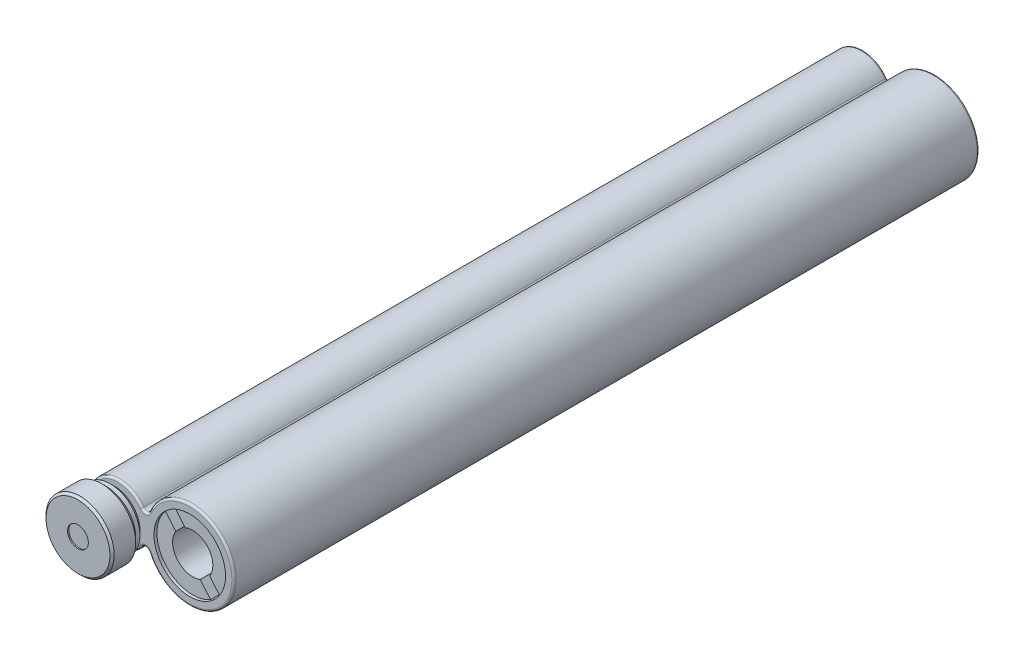
SolidWorks part; units mm, degrees
ref_plane "Front Plane" through (0, 0, 0) normal (0, 0, 1) x (1, 0, 0)
ref_plane "Top Plane" through (0, 0, 0) normal (0, 1, 0) x (1, 0, 0)
ref_plane "Right Plane" through (0, 0, 0) normal (1, 0, 0) x (0, 0, -1)
sketch "Sketch2" plane through (0, 0, 0) normal (0, 0, 1) x (1, 0, 0)
  line L0 (10.45, 0) -> (-23.95, 0) construction
  arc A0 (-10.2912, -1.815) -> (-10.2912, 1.815) centre (0, 0) ccw
  arc A1 (-10.2912, 1.815) -> (-10.2912, -1.815) centre (-17, 0) ccw
  dimension "D1" = 20.9
  dimension "D2" = 13.9
  dimension "D3" = 34.4
extrude "Extrude1" add sketch "Sketch2" along normal mid plane 176
fillet "Fillet1" radius 1 2 edges at (-10.2912, -1.815, 0) (-10.2912, 1.815, 0)
sketch "Sketch3" plane through (0, 0, 0) normal (0, 1, 0) x (1, 0, 0)
  line L0 (-17, 88.9319) -> (-17, -101.7378) construction
  line L2 (-20, -88) -> (-20, -88.8)
  line L4 (-23.95, -88) -> (-11.315, -88) construction
  line L5 (-20, -88.8) -> (-24.05, -88.8)
  line L6 (-24.05, -88.8) -> (-24.05, -90.8)
  line L7 (-24.05, -90.8) -> (-25.05, -90.8)
  line L8 (-25.05, -90.8) -> (-25.05, -97.4)
  line L9 (-25.05, -97.4) -> (-19.45, -97.4)
  line L10 (-19.45, -97.4) -> (-19.45, -97.1)
  line L11 (-19.45, -97.1) -> (-17, -97.1)
  line L12 (-17, -97.1) -> (-17, -88)
  line L13 (-17, -88) -> (-20, -88)
  dimension "D1" = 16.1
  dimension "D2" = 14.1
  dimension "D3" = 6
  dimension "D4" = 0.8
  dimension "D5" = 8.6
  dimension "D6" = 2
  dimension "D7" = 0.3
  dimension "D8" = 4.9
revolve "Revolve1" add sketch "Sketch3" angle 360 about L0
sketch "Sketch4" plane through (0, 0, 88) normal (0, 0, 1) x (1, 0, 0)
  circle A0 centre (0, 0) radius 8.45
  dimension "D1" = 16.9
extrude "Extrude2" cut sketch "Sketch4" against normal blind 0.7
sketch "Sketch5" plane through (0, 0, 87.3) normal (0, 0, 1) x (1, 0, 0)
  line L0 (-5.4056, 6.4948) -> (5.4056, -6.4948) construction
  line L1 (-6.4399, 5.4709) -> (-4.0081, 2.5491)
  line L2 (4.2109, -7.326) -> (1.7791, -4.4042)
  line L3 (6.4399, -5.4709) -> (4.0081, -2.5491)
  line L4 (-4.2109, 7.326) -> (-1.7791, 4.4042)
  circle A0 centre (0, 0) radius 8.45 construction
  arc A1 (4.0081, -2.5491) -> (-1.7791, 4.4042) centre (0, 0) ccw
  circle A2 centre (0, 0) radius 8.45 construction
  arc A3 (4.2109, -7.326) -> (6.4399, -5.4709) centre (0, 0) ccw
  arc A4 (-4.0081, 2.5491) -> (1.7791, -4.4042) centre (0, 0) ccw
  arc A5 (-4.2109, 7.326) -> (-6.4399, 5.4709) centre (0, 0) ccw
  point P4 (0, 0)
  dimension "D2" = 9.5
  dimension "D1" = 2.9
extrude "Extrude3" cut sketch "Sketch5" against normal blind 2.5
sketch "Sketch6" plane through (0, 0, 84.8) normal (0, 0, 1) x (1, 0, 0)
  circle A0 centre (0, 0) radius 4.75
extrude "Extrude4" cut sketch "Sketch6" against normal up to vertex (84.8 mm away) up to point (0, 0, 0)
mirror "Mirror1" about plane through (0, 0, 0) normal (0, 0, 1) of "Extrude4", "Extrude3", "Extrude2"
chamfer "Chamfer1" distance 1 angle 45 2 edges at (-24.05, 0, 88.8) (-25.05, 0, 90.8)
chamfer "Chamfer2" distance 0.5 angle 45 1 edges at (-25.05, 0, 97.4)
sketch "Sketch7" plane through (0, 0, -88) normal (0, 0, -1) x (-1, 0, 0)
  circle A0 centre (17, 0) radius 5.75
  dimension "D1" = 11.5
extrude "Extrude5" cut sketch "Sketch7" against normal blind 0.1
sketch "Sketch8" plane through (0, 0, -87.9) normal (0, 0, -1) x (-1, 0, 0)
  line L1 (19.3836, 2.5136) -> (16.015, 3.3211)
  line L2 (16.015, 3.3211) -> (13.6313, 0.8075)
  line L3 (13.6313, 0.8075) -> (14.6164, -2.5136)
  line L4 (14.6164, -2.5136) -> (17.985, -3.3211)
  line L5 (17.985, -3.3211) -> (20.3687, -0.8075)
  line L6 (20.3687, -0.8075) -> (19.3836, 2.5136)
  circle A0 centre (17, 0) radius 3 construction
  dimension "D1" = 6
extrude "Extrude6" cut sketch "Sketch8" against normal blind 9
fillet "Fillet2" radius 0.5 8 edges at (-10.3962, -3.5783, -88) (-23.95, 0, -88) (-10.3962, 3.5783, -88) (-10.3962, -3.5783, 88) (-23.95, 0, 88) (-10.3962, 3.5783, 88) (10.45, 0, -88) (10.45, 0, 88)
